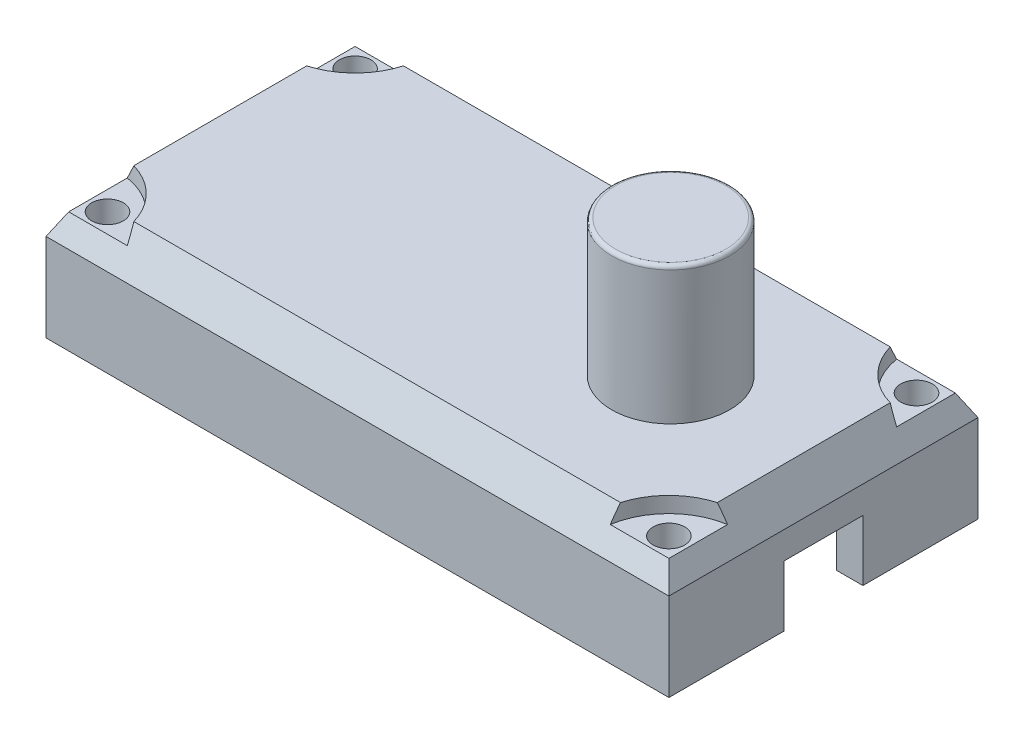
SolidWorks part; units mm, degrees
ref_plane "Front Plane" through (0, 0, 0) normal (0, 0, 1) x (1, 0, 0)
ref_plane "Top Plane" through (0, 0, 0) normal (0, 1, 0) x (1, 0, 0)
ref_plane "Right Plane" through (0, 0, 0) normal (1, 0, 0) x (0, 0, -1)
sketch "Sketch1" plane through (0, 0, 0) normal (0, 1, 0) x (1, 0, 0)
  line L1 (20.066, 9.9568) -> (-20.066, 9.9568)
  line L2 (20.066, 9.9568) -> (20.066, -9.9568)
  line L3 (20.066, -9.9568) -> (-20.066, -9.9568)
  line L4 (-20.066, 9.9568) -> (-20.066, -9.9568)
  line L5 (20.066, 9.9568) -> (-20.066, -9.9568) construction
  line L6 (20.066, -9.9568) -> (-20.066, 9.9568) construction
  point P0 (0, 0)
  dimension "D1" = 19.9136
  dimension "D2" = 40.132
extrude "Boss-Extrude1" add sketch "Sketch1" along normal blind 8.7122
shell "Shell1" thickness 1.7145 removed face at (0, 0, 0)
ref_plane "Plane2" through (0, 0, 0) normal (0, -1, 0) x (-1, 0, 0)
sketch "Sketch8" plane through (0, 0, 0) normal (0, -1, 0) x (-1, 0, 0)
  line L0 (0, -13.0536) -> (0, 17.6708) construction
  line L1 (27.4553, 0) -> (-28.1412, 0) construction
  line L2 (-20.066, 9.9568) -> (20.066, 9.9568) construction
  line L4 (20.066, 9.9568) -> (20.066, -9.9568) construction
  circle A0 centre (18.288, 8.1788) radius 1.778
  circle A1 centre (-18.288, 8.1788) radius 1.778
  circle A2 centre (18.288, -8.1788) radius 1.778
  circle A3 centre (-18.288, -8.1788) radius 1.778
sketch "Sketch2" plane through (0, 8.7122, 0) normal (0, 1, 0) x (1, 0, 0)
  line L1 (0, 15.3928) -> (0, -13.8045) construction
  line L2 (26.7949, 0) -> (-27.5388, 0) construction
  circle A0 centre (20.066, 9.9568) radius 4.5674
  circle A1 centre (-20.066, 9.9568) radius 4.5674
  circle A2 centre (-20.066, -9.9568) radius 4.5674
  circle A3 centre (20.066, -9.9568) radius 4.5674
sketch "Sketch3" plane through (0, 8.7122, 0) normal (0, 1, 0) x (1, 0, 0)
  line L1 (20.066, -9.9568) -> (20.066, 9.9568) construction
  circle A0 centre (10.2235, 0) radius 3.8
  dimension "D2" = 7.6
  dimension "D1" = 9.8425
extrude "Boss-Extrude2" add sketch "Sketch3" along normal blind 8.84
extrude "Boss-Extrude5" add sketch "Sketch8" against normal up to surface (6.9977 mm away) up to face at (0, 6.9977, 0)
sketch "Sketch7" plane through (0, 0, 0) normal (0, -1, 0) x (-1, 0, 0)
  line L0 (0, -16.1532) -> (0, 17.3006) construction
  line L1 (28.752, 0) -> (-28.1196, 0) construction
  line L2 (-20.066, 9.9568) -> (20.066, 9.9568) construction
  line L3 (20.066, 9.9568) -> (20.066, -9.9568) construction
  circle A0 centre (18.0848, 7.9756) radius 1.016
  circle A1 centre (-18.0848, 7.9756) radius 1.016
  circle A2 centre (18.0848, -7.9756) radius 1.016
  circle A3 centre (-18.0848, -7.9756) radius 1.016
  dimension "D1" = 2.032
  dimension "D2" = 1.9812
  dimension "D3" = 1.9812
extrude "Cut-Extrude5" cut sketch "Sketch7" against normal up to surface (8.7122 mm away) up to face at (10.2235, 8.7122, -3.8)
chamfer "Chamfer1" distance 2.3876 distance2 1.27 4 edges at (20.066, 8.7122, 0) (0, 8.7122, -9.9568) (-20.066, 8.7122, 0) (0, 8.7122, 9.9568) first distance on face at (20.066, 4.3561, 0) first distance on face at (0, 4.3561, -9.9568) first distance on face at (-20.066, 4.3561, 0) first distance on face at (0, 4.3561, 9.9568)
extrude "Cut-Extrude6" cut sketch "Sketch2" against normal blind 1.016
sketch "Sketch10" plane through (0, 0, 0) normal (0, -1, 0) x (-1, 0, 0)
  line L5 (19.6402, -9.337) -> (-19.6402, 9.337) construction
  line L6 (19.7672, 0) -> (-19.6402, 0) construction
  line L7 (20.193, -9.9568) -> (-20.066, -9.9568)
  line L8 (20.193, -9.9568) -> (20.193, 9.9568)
  line L9 (20.193, 9.9568) -> (-20.066, 9.9568)
  line L10 (-20.066, -9.9568) -> (-20.066, 9.9568)
  line L11 (20.193, -9.9568) -> (-20.066, 9.9568) construction
  line L12 (20.193, 9.9568) -> (-20.066, -9.9568) construction
  point P0 (0, 0)
  point P6 (0.0635, 0)
extrude "Cut-Extrude7" cut sketch "Sketch10" against normal blind 0.6604
sketch "Sketch11" plane through (20.066, 0, 0) normal (1, 0, 0) x (0, 0, -1)
  line L0 (0, -2.5512) -> (0, 13.0859) construction
  line L1 (-55, 0) -> (55, 0) construction
  line L2 (-2.54, 4.572) -> (2.54, 4.572)
  line L3 (-2.54, 4.572) -> (-2.54, 0)
  line L4 (-2.54, 0) -> (2.54, 0)
  line L5 (2.54, 4.572) -> (2.54, 0)
  line L6 (-2.54, 4.572) -> (2.54, 0) construction
  line L7 (-2.54, 0) -> (2.54, 4.572) construction
  point P3 (0, 2.286)
  dimension "D1" = 5.08
  dimension "D2" = 4.572
extrude "Cut-Extrude8" cut sketch "Sketch11" against normal up to surface (1.7145 mm away) up to face at (18.3515, 3.8291, 0)
sketch "Sketch12" plane through (0, 0, 0) normal (0, -1, 0) x (-1, 0, 0)
  line L0 (-25.0797, 0) -> (28.5864, 0) construction
  line L1 (6.3572, -8.5725) -> (12.4234, -8.5725) construction
  line L4 (18.8722, 1.9377) -> (18.8722, -1.9346) construction
  circle A0 centre (10.2997, 0) radius 8.5725
  dimension "D1" = 17.145
extrude "Cut-Extrude9" cut sketch "Sketch12" against normal up to surface (6.9977 mm away) up to face at (0, 6.9977, 0)
fillet "Fillet1" radius 0.25 1 edges at (10.2235, 17.5522, 3.8)
